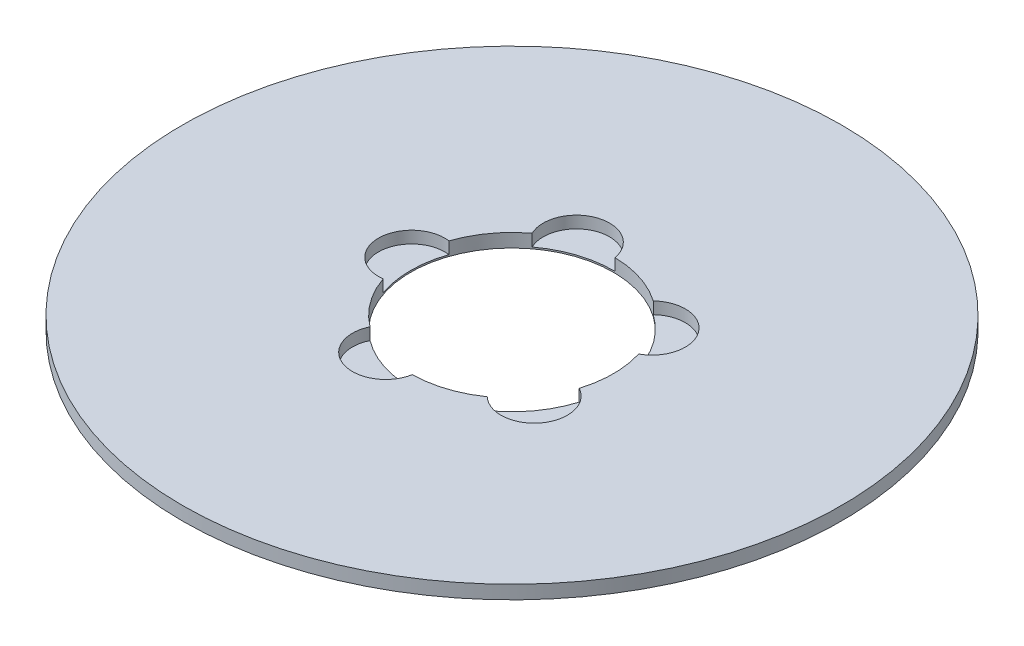
SolidWorks part; units mm, degrees
ref_plane "Front Plane" through (0, 0, 0) normal (0, 0, 1) x (1, 0, 0)
ref_plane "Top Plane" through (0, 0, 0) normal (0, 1, 0) x (1, 0, 0)
ref_plane "Right Plane" through (0, 0, 0) normal (1, 0, 0) x (0, 0, -1)
sketch "Sketch1" plane through (0, 0, 0) normal (0, 1, 0) x (1, 0, 0)
  circle A0 centre (0, 0) radius 97.5
  dimension "FLANGE_OD" = 195
extrude "Boss-Extrude1" add sketch "Sketch1" along normal blind 4
sketch "Sketch2" plane through (0, 0, 0) normal (0, 1, 0) x (1, 0, 0)
  circle A0 centre (0, 0) radius 30
  dimension "BORE_D" = 60
extrude "Cut-Extrude1" cut sketch "Sketch2" along normal through all
sketch "Sketch3" plane through (0, 4, 0) normal (0, 1, 0) x (1, 0, 0)
  circle A0 centre (0, 0) radius 29.6757 construction
  circle A1 centre (-29.6757, 0) radius 9.8234
  dimension "BOLT_D" = 19.6468
  dimension "BOLT_PCD" = 59.3515
extrude "Cut-Extrude2" cut sketch "Sketch3" against normal blind 3.5319
pattern_circular "CirPattern1" count 5 over 360 about axis through (0, 0, 0) along (0, 1, 0) of "Cut-Extrude2"
